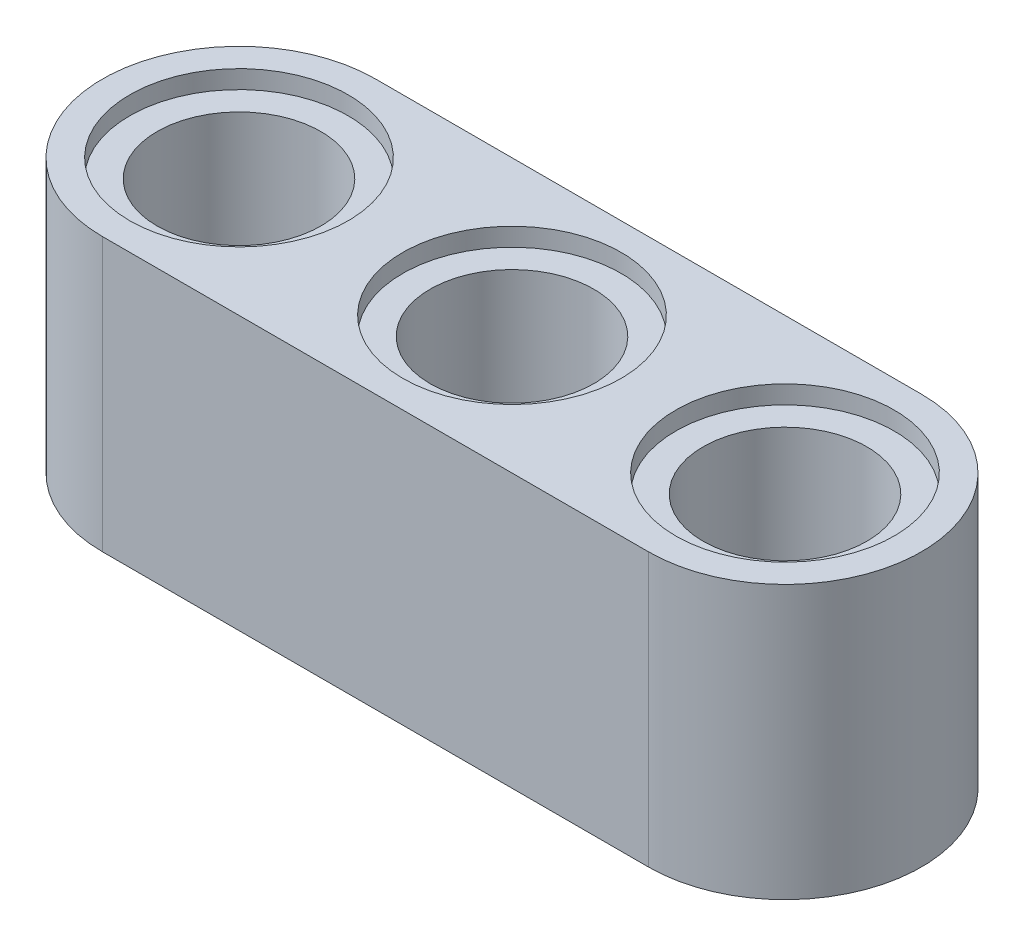
SolidWorks part; units mm, degrees
ref_plane "Front Plane" through (0, 0, 0) normal (0, 0, 1) x (1, 0, 0)
ref_plane "Top Plane" through (0, 0, 0) normal (0, 1, 0) x (1, 0, 0)
ref_plane "Right Plane" through (0, 0, 0) normal (1, 0, 0) x (0, 0, -1)
sketch "Sketch1" plane through (0, 0, 0) normal (0, 1, 0) x (1, 0, 0)
  line L1 (0, 0) -> (15, 0)
  line L2 (0, 0) -> (0, 5)
  line L3 (0, 5) -> (15, 5)
  line L4 (15, 0) -> (15, 5)
  circle A0 centre (2.5, 2.5) radius 2.5
  circle A1 centre (12.5, 2.5) radius 2.5
  circle A2 centre (2.5, 2.5) radius 1.5
  circle A3 centre (2.5, 2.5) radius 2
  circle A4 centre (7.5, 2.5) radius 2
  circle A5 centre (7.5, 2.5) radius 1.5
  circle A6 centre (12.5, 2.5) radius 2
  circle A7 centre (12.5, 2.5) radius 1.5
  dimension "D3" = 3
  dimension "D4" = 4
  dimension "D1" = 5
  dimension "D2" = 15
  dimension "D5" = 3
extrude "Boss-Extrude3" add sketch "Sketch1" along normal blind 2.5 contours A1 L3 A0 L1 A4 | A0 A3 | A3 A2 | A1 A6 | A6 A7 | A4 A5 region at (4.3468, 0, -0.6532) region at (0.7822, 0, -0.7822) region at (10.0707, 0, -2.5) region at (0.5566, 0, -2.5) region at (5.5566, 0, -2.5) region at (10.5566, 0, -2.5)
extrude "Cut-Extrude1" cut sketch "Sketch1<5>" along normal blind 0.3333 contours A6 A7 | A4 A5 | A3 A2 region at (0.5566, 0, -2.5) region at (5.5566, 0, -2.5) region at (10.5566, 0, -2.5)
sketch "Sketch1<5>" plane through (0, 0, 0) normal (0, 1, 0) x (1, 0, 0) same geometry as "Sketch1"
mirror "Mirror2" about plane through (0, 2.5, 0) normal (0, 1, 0) of "Boss-Extrude3", "Cut-Extrude1"
